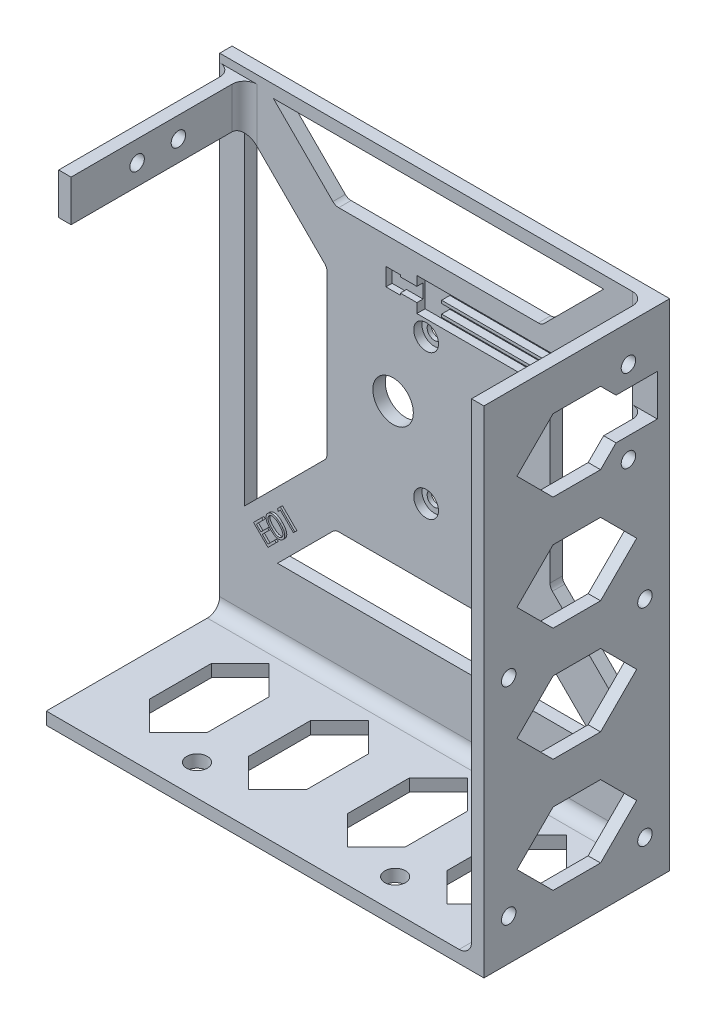
SolidWorks part; units mm, degrees
ref_plane "Front Plane" through (0, 0, 0) normal (0, 0, 1) x (1, 0, 0)
ref_plane "Top Plane" through (0, 0, 0) normal (0, 1, 0) x (1, 0, 0)
ref_plane "Right Plane" through (0, 0, 0) normal (1, 0, 0) x (0, 0, -1)
sketch "Sketch1" plane through (0, 0, 0) normal (0, 0, 1) x (1, 0, 0)
  line L1 (-50, 50) -> (50, 50)
  line L2 (-50, 50) -> (-50, -50)
  line L3 (-50, -50) -> (50, -50)
  line L4 (50, 50) -> (50, -50)
  line L5 (-50, 50) -> (50, -50) construction
  line L6 (-50, -50) -> (50, 50) construction
  line L7 (-47, 38) -> (-27, 18)
  line L8 (-27, 18) -> (-27, -22)
  line L9 (-27, -22) -> (-47, -42)
  line L11 (-47, 38) -> (-47, -42)
  line L12 (0, -50) -> (0, 50) construction
  line L13 (47, 38) -> (27, 18)
  line L14 (27, 18) -> (27, -22)
  line L15 (27, -22) -> (47, -42)
  line L16 (47, 38) -> (47, -42)
  line L17 (-40, 47) -> (40, 47)
  line L18 (40, 47) -> (25, 32)
  line L19 (25, 32) -> (-25, 32)
  line L20 (-25, 32) -> (-40, 47)
  line L21 (-228.5647, -2) -> (-128.5647, -2) construction
  line L22 (25, -36) -> (-25, -36)
  line L23 (40, -51) -> (25, -36)
  line L24 (-40, -51) -> (40, -51)
  line L25 (-25, -36) -> (-40, -51)
  line L26 (50, -50) -> (50, -70)
  line L31 (50, 50) -> (53, 50)
  line L32 (50, 50) -> (50, -50)
  line L33 (50, -50) -> (53, -50)
  line L34 (53, 50) -> (53, -50)
  line L35 (-50, 50) -> (-53, 50)
  line L36 (-50, 50) -> (-50, -50)
  line L37 (-50, -50) -> (-53, -50)
  line L38 (-53, 50) -> (-53, -50)
  line L39 (-53, -50) -> (53, -50)
  line L40 (-53, -50) -> (-53, -70)
  line L41 (-53, -50) -> (53, -50)
  line L42 (-53, -70) -> (53, -70)
  line L43 (53, -50) -> (53, -70)
  circle A2 centre (-11, -2) radius 4.9
  circle A3 centre (-3, 15.5) radius 1.75
  circle A4 centre (-3, -19.5) radius 1.75
  point P0 (0, 0)
  point P5 (0, 0)
  point P23 (0, 47)
  point P41 (0, 0)
  point P43 (0, 0)
  point P44 (0, 0)
  point P45 (0, 0)
  point P46 (-53, 0)
  point P47 (0, 0)
  point P48 (0, 0)
  point P50 (-27, -2)
  dimension "D16" = 9.8
  dimension "D14" = 3.5
  dimension "D1" = 100
  dimension "D2" = 100
  dimension "D3" = 80
  dimension "D4" = 45
  dimension "D5" = 20
  dimension "D6" = 3
  dimension "D7" = 3
  dimension "D8" = 45
  dimension "D9" = 80
  dimension "D10" = 15
  dimension "D11" = 3
  dimension "D13" = 17.5
  dimension "D12" = 39
  dimension "D15" = 8
  dimension "D17" = 45
  dimension "D18" = 45
  dimension "D19" = 3
  dimension "D20" = 20
  dimension "D21" = 2
extrude "Base" add sketch "Sketch1" along normal blind 3 contours L1 L34 L16 L3 L4 | L40 L39 L43 L42 | L36 L35 L38 L37 | L32 L31 L34 L33 region at (0.1575, 0.8696, 0)
sketch "Sketch6" plane through (0, 0, 3) normal (0, 0, 1) x (1, 0, 0)
  line L0 (40, 47) -> (47, 38) construction
  line L1 (-47, -42) -> (-39, -50) construction
  line L2 (-41.2374, -47.7626) -> (45.9172, 39.3921) construction
  line L3 (47, 38) -> (27, 18) construction
  text T0 "E01" font "Century Gothic" height 5
  point P6 (0, 0)
  point P7 (0, 0)
  dimension "D1" = 1.75
extrude "Revision" add sketch "Sketch6" along normal blind 0.5
sketch "Sketch3" plane through (0, 0, 3) normal (0, 0, 1) x (1, 0, 0)
  circle A0 centre (-3, 15.5) radius 3
  circle A1 centre (-3, -19.5) radius 3
  dimension "D1" = 6
  dimension "D2" = 6
extrude "Stepper_Holes" cut sketch "Sketch3" against normal blind 2
sketch "Sketch4" plane through (0, 0, 3) normal (0, 0, 1) x (1, 0, 0)
  line L0 (-11, -2) -> (-50.929, -2)
  line L1 (-50.929, -2) -> (-50.929, 38.2605)
  dimension "D1" = 39.929
  dimension "D2" = 40.2605
sketch "Sketch5" plane through (0, 0, 3) normal (0, 0, 1) x (1, 0, 0)
  line L0 (-50, 48) -> (-50, 38)
  line L2 (-50, 38) -> (-47, 38)
  line L6 (-47, 48) -> (-50, 48)
  line L7 (-47, 38) -> (-47, 48)
  line L8 (-53, 0) -> (0, 0) construction
  dimension "D1" = 10
  dimension "D2" = 3
extrude "Front_Tower" add sketch "Sketch5" along normal blind 42
sketch "Sketch8" plane through (-47, 0, 0) normal (1, 0, 0) x (0, 0, -1)
  line L1 (-45, 48) -> (-3, 48) construction
  line L2 (-24, 48) -> (-24, 38) construction
  line L3 (-45, 38) -> (-3, 38) construction
  circle A1 centre (-29, 43) radius 1.75
  circle A2 centre (-19, 43) radius 1.75
  point P13 (-24, 43)
  dimension "D1" = 3.5
  dimension "D2" = 5
extrude "Flip_Holder_Cut" cut sketch "Sketch8" against normal up to surface (3 mm away) up to face at (-50, 43, 24)
sketch "Sketch10" plane through (0, 0, 3) normal (0, 0, 1) x (1, 0, 0)
  line L7 (-53, -70) -> (53, -70)
  line L9 (53, -70) -> (53, 50)
  line L10 (53, 50) -> (50, 50)
  line L11 (-53, 50) -> (53, 50) construction
  line L12 (50, 50) -> (50, -67)
  line L13 (50, -67) -> (-53, -67)
  line L14 (-53, 50) -> (-53, -70) construction
  line L15 (-53, -67) -> (-53, -70)
  dimension "D1" = 3
extrude "Boss-Extrude1" add sketch "Sketch10" along normal blind 42
fillet "Fillet-2mm" radius 2 8 edges at (25, 32, 1.5) (-25, 32, 1.5) (-27, 18, 1.5) (27, 18, 1.5) (27, -22, 1.5) (-27, -22, 1.5) (25, -36, 1.5) (-25, -36, 1.5)
sketch "Sketch11" plane through (53, 0, 0) normal (1, 0, 0) x (0, 0, -1)
sketch "Sensor" plane through (0, 0, 3) normal (0, 0, 1) x (1, 0, 0)
  line L1 (-12.75, 21.1) -> (-9.25, 21.1)
  line L2 (-12.75, 21.1) -> (-12.75, 25.4)
  line L3 (-12.75, 25.4) -> (-9.25, 25.4)
  line L4 (-9.25, 21.1) -> (-9.25, 21.55)
  line L10 (-5.25, 24.95) -> (-5.25, 27.25)
  line L13 (-9.25, 24.95) -> (-5.25, 24.95)
  line L14 (0.75, 21.45) -> (0.75, 22.15)
  line L16 (-5.25, 21.55) -> (-9.25, 21.55)
  line L17 (-9.25, 24.95) -> (-9.25, 25.4)
  line L18 (-5.25, 27.25) -> (36.25, 27.25)
  line L21 (36.25, 19.25) -> (-5.25, 19.25)
  line L22 (-5.25, 19.25) -> (-5.25, 21.55)
  line L24 (36.25, 21.45) -> (0.75, 21.45)
  line L26 (0.75, 22.15) -> (36.25, 22.15)
  line L27 (36.25, 24.35) -> (0.75, 24.35)
  line L29 (0.75, 25.05) -> (36.25, 25.05)
  line L30 (36.25, 25.05) -> (36.25, 27.25)
  line L31 (36.25, 22.15) -> (36.25, 24.35)
  line L32 (36.25, 21.45) -> (36.25, 19.25)
  line L33 (0.75, 24.35) -> (0.75, 25.05)
  line L34 (47, 38) -> (27.5858, 18.5858) construction
  point P4 (-12.75, 23.25)
  point P5 (36.25, 23.25)
  point P6 (-11, 21.1)
  dimension "D7" = 2.2
  dimension "D1" = 3.5
  dimension "D2" = 4.3
  dimension "D3" = 3.4
  dimension "D4" = 4
  dimension "D5" = 2.2
  dimension "D6" = 25.25
  dimension "D8" = 2.2
  dimension "D9" = 6
  dimension "D10" = 8
extrude "Sensor_Cut" cut sketch "Sensor" against normal blind 1.5
sketch "Sketch21" plane through (0, 0, 1.5) normal (0, 0, 1) x (1, 0, 0)
  line L0 (-5.25, 27.25) -> (-5.25, 19.25)
  line L1 (-5.25, 19.25) -> (28.25, 19.25)
  line L2 (28.25, 19.25) -> (30.45, 21.45)
  line L3 (30.45, 21.45) -> (0.75, 21.45)
  line L4 (0.75, 21.45) -> (0.75, 22.15)
  line L5 (0.75, 22.15) -> (31.15, 22.15)
  line L6 (31.15, 22.15) -> (33.35, 24.35)
  line L7 (33.35, 24.35) -> (0.75, 24.35)
  line L8 (0.75, 24.35) -> (0.75, 25.05)
  line L9 (0.75, 24.35) -> (0.75, 25.05) construction
  line L10 (0.75, 25.05) -> (34.05, 25.05)
  line L11 (34.05, 25.05) -> (36.25, 27.25)
  line L12 (36.25, 27.25) -> (-5.25, 27.25)
extrude "Sensor_Wire_Trench_Cut" cut sketch "Sketch21" against normal blind 0.5
sketch "Sketch16" plane through (0, 50, 0) normal (0, 1, 0) x (1, 0, 0)
  line L0 (51, -12) -> (51.5, -12.8)
  line L1 (52, -5) -> (51, -5)
  line L2 (52, -5) -> (52, -12)
  line L4 (51, -5) -> (51, -12)
  line L5 (51.5, -12.8) -> (52, -12)
  line L6 (-55, 0) -> (55, 0) construction
  line L7 (50, -45) -> (50, -3) construction
  line L8 (53, -45) -> (53, 0) construction
  dimension "D1" = 5
  dimension "D3" = 1
  dimension "D4" = 1
  dimension "D2" = 0.8
  dimension "D6" = 7
extrude "Wire_Channel_Cut" [suppressed] cut sketch "Sketch16" against normal up to surface and the other way through all up to face at (0, -70, 22.5)
fillet "Fillet-0.5mm" [suppressed] radius 0.5
fillet "Fillet-3mm" radius 3 5 edges at (50, -8.5, 3) (-1.5, -67, 3) (-47, 43, 3) (-50, 43, 3) (50, -67, 24)
sketch "Sketch17" plane through (53, 0, 0) normal (1, 0, 0) x (0, 0, -1)
  line L0 (-45, -70) -> (0, -70) construction
  line L1 (0, 55) -> (0, -55) construction
  line L2 (-8, -51.25) -> (-16.75, -60)
  line L3 (-16.75, -60) -> (-28.25, -60)
  line L4 (-28.25, -60) -> (-37, -51.25)
  line L5 (-37, -51.25) -> (-28.25, -42.5)
  line L6 (-28.25, -42.5) -> (-16.75, -42.5)
  line L7 (-16.75, -42.5) -> (-8, -51.25)
  line L8 (-45, -70) -> (-45, 50) construction
  line L9 (-16.75, -15) -> (-8, -23.75)
  line L10 (-8, -23.75) -> (-16.75, -32.5)
  line L11 (-16.75, -32.5) -> (-28.25, -32.5)
  line L12 (-28.25, -32.5) -> (-37, -23.75)
  line L13 (-37, -23.75) -> (-28.25, -15)
  line L14 (-28.25, -15) -> (-16.75, -15)
  line L15 (-16.75, 12.5) -> (-8, 3.75)
  line L16 (-8, 3.75) -> (-16.75, -5)
  line L17 (-16.75, -5) -> (-28.25, -5)
  line L18 (-28.25, -5) -> (-37, 3.75)
  line L19 (-37, 3.75) -> (-28.25, 12.5)
  line L20 (-28.25, 12.5) -> (-16.75, 12.5)
  line L21 (-16.75, 40) -> (-8, 31.25)
  line L22 (-8, 31.25) -> (-16.75, 22.5)
  line L23 (-16.75, 22.5) -> (-28.25, 22.5)
  line L24 (-28.25, 22.5) -> (-37, 31.25)
  line L25 (-37, 31.25) -> (-28.25, 40)
  line L26 (-28.25, 40) -> (-16.75, 40)
  dimension "D6" = 8
  dimension "D7" = 8
  dimension "D8" = 17.5
  dimension "D9" = 90
  dimension "D10" = 10
  dimension "D11" = 4
extrude "Back_Hexagon" cut sketch "Sketch17" against normal up to surface (3 mm away) up to face at (50, -7, 25.5)
sketch "Sketch18" plane through (53, 0, 0) normal (1, 0, 0) x (0, 0, -1)
  line L3 (-3, 36.25) -> (-3, 26.25)
  line L4 (-3, 26.25) -> (-13, 26.25)
  line L5 (-16.75, 22.5) -> (-8, 31.25) construction
  line L6 (-13, 26.25) -> (-13, 36.25)
  line L8 (-13, 36.25) -> (-3, 36.25)
  line L12 (0, 55) -> (0, -55) construction
  point P0 (-13, 31.25)
  dimension "D1" = 10
  dimension "D3" = 3
extrude "Back_Wire" cut sketch "Sketch18" against normal blind 10
sketch "Sketch19" plane through (53, 0, 0) normal (1, 0, 0) x (0, 0, -1)
  line L0 (-45, -70) -> (0, -70) construction
  line L1 (0, 55) -> (0, -55) construction
  line L3 (-3, 36.25) -> (-13, 36.25) construction
  line L4 (-13, 26.25) -> (-3, 26.25) construction
  line L5 (-3, -2) -> (-3, 38.2605) construction
  circle A0 centre (-6, -60) radius 1.75
  circle A1 centre (-39, -60) radius 1.75
  circle A2 centre (-39, -10) radius 1.75
  circle A3 centre (-6, -10) radius 1.75
  circle A4 centre (-10, 21.25) radius 1.75
  circle A5 centre (-10, 41.25) radius 1.75
  dimension "D1" = 3.5
  dimension "D9" = 3.5
  dimension "D10" = 3.5
  dimension "D2" = 10
  dimension "D3" = 6
  dimension "D6" = 5
  dimension "D7" = 5
  dimension "D8" = 7
  dimension "D11" = 20
  dimension "D12" = 50
  dimension "D13" = 33
  dimension "D4" = 2
  dimension "D5" = 2
extrude "Back_Holes" cut sketch "Sketch19" against normal up to surface (3 mm away) up to face at (50, -51.25, 22.5)
sketch "Sketch20" plane through (50, 0, 0) normal (-1, 0, 0) x (0, 0, 1)
  line L0 (9, -6) -> (3, -6)
  line L1 (9, -56) -> (3, -56)
  line L2 (9, -56) -> (9, -64)
  line L3 (9, -64) -> (3, -64)
  line L4 (3, -56) -> (3, -64)
  line L5 (9, -6) -> (9, -14)
  line L6 (9, -14) -> (3, -14)
  line L7 (3, -6) -> (3, -14)
  point P4 (6, -56)
  point P6 (9, -60)
  point P12 (6, -6)
  point P13 (9, -10)
  dimension "D1" = 6
  dimension "D2" = 8
  dimension "D3" = 8
  dimension "D4" = 6
extrude "Back_Fillet_Clear" cut sketch "Sketch20" along normal blind 10
sketch "Sketch12" plane through (0, -70, 0) normal (0, -1, 0) x (1, 0, 0)
  line L3 (-53, 45) -> (-53, 0) construction
  line L10 (-43, 30) -> (-43, 15)
  line L14 (-43, 15) -> (-36, 8)
  line L15 (-36, 8) -> (-29, 15)
  line L16 (-29, 15) -> (-29, 30)
  line L17 (-29, 30) -> (-36, 37)
  line L18 (-36, 37) -> (-43, 30)
  line L19 (-53, 0) -> (53, 0) construction
  line L20 (-19, 30) -> (-19, 15)
  line L21 (-19, 15) -> (-12, 8)
  line L22 (-12, 8) -> (-5, 15)
  line L23 (-5, 15) -> (-5, 30)
  line L24 (-5, 30) -> (-12, 37)
  line L25 (-12, 37) -> (-19, 30)
  line L26 (5, 30) -> (5, 15)
  line L27 (5, 15) -> (12, 8)
  line L28 (12, 8) -> (19, 15)
  line L29 (19, 15) -> (19, 30)
  line L30 (19, 30) -> (12, 37)
  line L31 (12, 37) -> (5, 30)
  line L32 (29, 30) -> (29, 15)
  line L33 (29, 15) -> (36, 8)
  line L34 (36, 8) -> (43, 15)
  line L35 (43, 15) -> (43, 30)
  line L36 (43, 30) -> (36, 37)
  line L37 (36, 37) -> (29, 30)
  line L38 (-43, 30) -> (-19, 30) construction
  point P0 (-43, 22.5)
  point P5 (-53, 22.5)
  dimension "D1" = 8
  dimension "D2" = 4
  dimension "D3" = 24
  dimension "D4" = 10
  dimension "D5" = 14
extrude "Bottom_Cut" cut sketch "Sketch12" against normal up to surface (3 mm away) up to face at (-3, -67, 25.5)
sketch "Sketch23" plane through (0, -70, 0) normal (0, -1, 0) x (1, 0, 0)
  line L2 (-29, 15) -> (-29, 30) construction
  line L3 (-19, 30) -> (-19, 15) construction
  line L4 (-29, 22.5) -> (-19, 22.5) construction
  line L5 (19, 22.5) -> (29, 22.5) construction
  line L6 (19, 15) -> (19, 30) construction
  line L7 (29, 30) -> (29, 15) construction
  line L8 (-53, 45) -> (53, 45) construction
  circle A0 centre (-24, 37.5) radius 2.5
  circle A1 centre (24, 37.5) radius 2.5
  point P16 (-24, 22.5)
  point P17 (24, 22.5)
  dimension "D1" = 5
  dimension "D2" = 5
  dimension "D3" = 7.5
  dimension "D4" = 7.5
extrude "Cut-Extrude1" cut sketch "Sketch23" against normal up to surface (3 mm away) up to face at (36, -67, 22.5)
equation "\"D3@Sketch1\"=\"D2@Sketch1\"*.8"
equation "\"D9@Sketch1\"=\"D1@Sketch1\"*.8"
equation "\"ServoDriverBoard_Width\"= 26.6mm"
equation "\"ServoDriverBoard_Length\"= 29.6mm"
equation "\"ServoDriverBoard_FromTop\"= 5mm"
equation "\"ServoDriverBoard_HoleSize\"= 3.3mm"
equation "\"Frame Size\"= 100mm"
equation "\"D1@Sketch1\"=\"Frame Size\""
equation "\"D2@Sketch3\"=\"D1@Sketch3\""
equation "\"Flip Y Offset\"= 36 * sin ( 3.6 )"
equation "\"Flip X Position\"= 36 * cos ( 3.6 )"
equation "\"Flip Length\"= 38mm"
equation "\"D2@Sketch4\"=\"Flip Y Offset\"+\"Flip Length\""
equation "\"D4@Sketch16\"=\"D3@Sketch16\""
